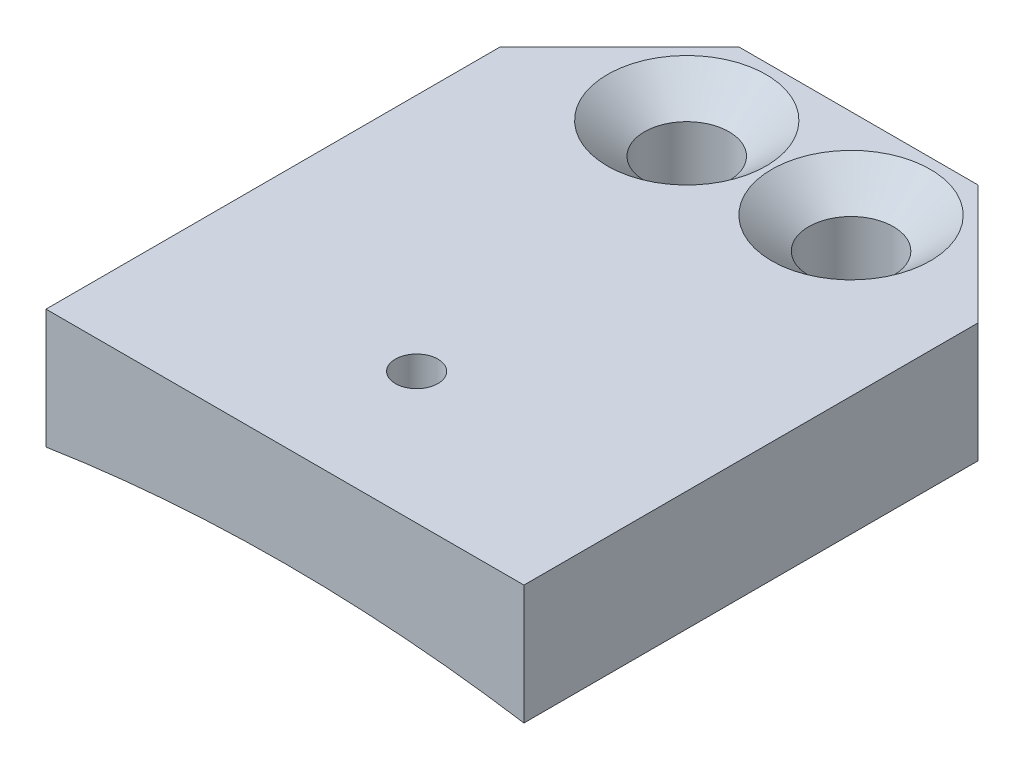
SolidWorks part; units mm, degrees
ref_plane "Front Plane" through (0, 0, 0) normal (0, 0, 1) x (1, 0, 0)
ref_plane "Top Plane" through (0, 0, 0) normal (0, 1, 0) x (1, 0, 0)
ref_plane "Right Plane" through (0, 0, 0) normal (1, 0, 0) x (0, 0, -1)
sketch "Sketch1" plane through (0, 0, 0) normal (0, 1, 0) x (1, 0, 0)
  line L0 (-28.5118, 11.5753) -> (-22.1618, 17.9253)
  line L1 (-22.1618, 17.9253) -> (-9.4618, 17.9253)
  line L2 (-28.5118, 11.5753) -> (-28.5118, -12.5547)
  line L3 (-28.5118, -12.5547) -> (-3.1118, -12.5547)
  line L4 (-3.1118, 11.5753) -> (-3.1118, -12.5547)
  line L5 (-9.4618, 17.9253) -> (-3.1118, 11.5753)
  line L6 (-15.8118, -12.5547) -> (-15.8118, 17.9253) construction
  line L8 (-3.1118, 11.5753) -> (-3.1118, 17.9253) construction
  line L9 (-3.1118, 17.9253) -> (-9.4618, 17.9253) construction
  dimension "D1" = 12.7
  dimension "D2" = 30.48
  dimension "D3" = 25.4
extrude "Boss-Extrude1" add sketch "Sketch1" along normal blind 6.35
sketch "Sketch2" plane through (0, 0, 12.5547) normal (0, 0, 1) x (1, 0, 0)
  circle A0 centre (-15.8118, -81.0531) radius 82.042
  dimension "D1" = 164.084
hole_wizard "CSK for #8 Flat Head Machine Screw (100)1" positions "Sketch3" profile "Sketch4" countersink size "#8" standard "ANSI Inch" end condition through all
sketch "Sketch3" plane through (0, 6.35, 0) normal (0, 1, 0) x (1, 0, 0)
  line L0 (-15.8118, 17.9253) -> (-15.8118, 3.4006) construction
  line L1 (-9.4618, 17.9253) -> (-22.1618, 17.9253) construction
  point P0 (-20.1775, 13.1628)
  point P12 (-11.4462, 13.1628)
  dimension "D1" = 4.7625
  dimension "D2" = 4.3656
sketch "Sketch4" plane through (-20.1775, 6.35, -13.1628) normal (1, 0, 0) x (0, 0, 1)
  line L0 (0, 0) -> (0, 6.35)
  line L1 (0, 6.35) -> (2.2479, 6.35)
  line L2 (2.2479, 6.35) -> (2.2479, 1.6518)
  line L3 (2.2479, 1.6518) -> (4.2164, 0)
  line L5 (4.2164, 0) -> (0, 0)
  line L6 (-2.2479, 1.6518) -> (-4.2164, 0) construction
  line L11 (0, -6.35) -> (0, 107.95) construction
  dimension "Thru Hole Dia." = 4.4958
  dimension "Thru Hole Depth" = 6.35
  dimension "Near C'Sink Dia." = 8.4328
  dimension "Near C'Sink Angle" = 100
extrude "Cut-Extrude1" cut sketch "Sketch2" against normal through all
sketch "Sketch5" plane through (0, 6.35, 0) normal (0, 1, 0) x (1, 0, 0)
  line L1 (-28.5118, 11.5753) -> (-28.5118, -12.5547) construction
  line L2 (-9.4618, 17.9253) -> (-22.1618, 17.9253) construction
  circle A0 centre (-15.7994, -5.5697) radius 1.1303
  point P3 (0, 0)
  dimension "D3" = 2.2606
  dimension "D4" = 12.7124
  dimension "D5" = 23.495
extrude "Cut-Extrude2" cut sketch "Sketch5" against normal through all
